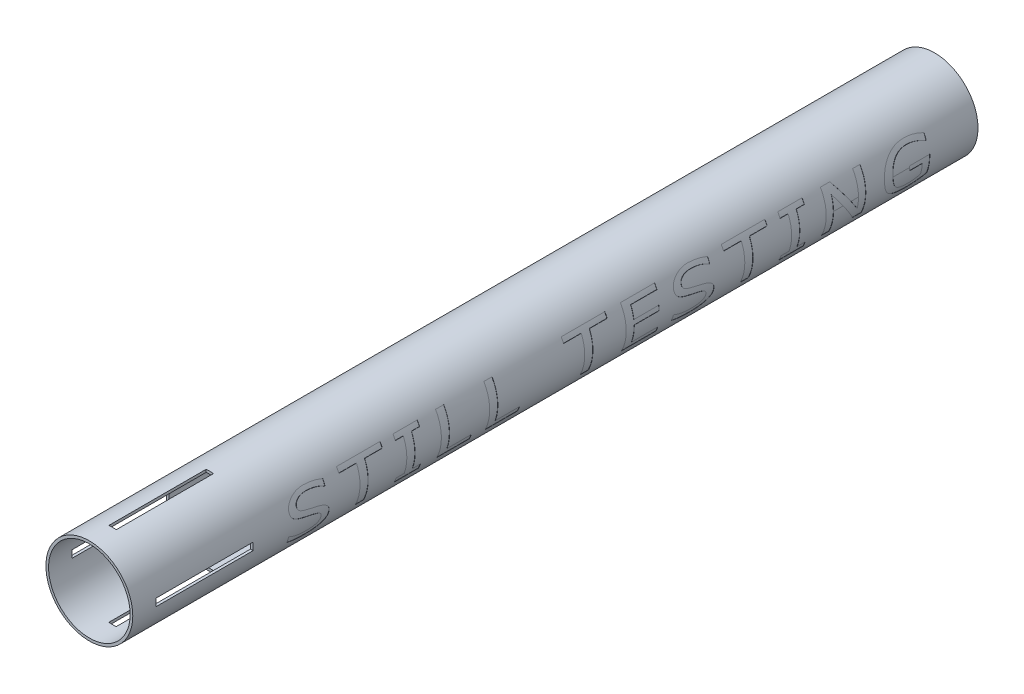
SolidWorks part; units mm, degrees
ref_plane "Front Plane" through (0, 0, 0) normal (0, 0, 1) x (1, 0, 0)
ref_plane "Top Plane" through (0, 0, 0) normal (0, 1, 0) x (1, 0, 0)
ref_plane "Right Plane" through (0, 0, 0) normal (1, 0, 0) x (0, 0, -1)
sketch "Sketch1" plane through (0, 0, 0) normal (0, 0, 1) x (1, 0, 0)
  circle A0 centre (0, 0) radius 20.555
  circle A1 centre (0, 0) radius 19.305
  dimension "D1" = 41.11
  dimension "D2" = 38.61
extrude "Boss-Extrude3" add sketch "Sketch1" against normal blind 400
sketch "Sketch2" plane through (0, 0, 0) normal (0, 1, 0) x (1, 0, 0)
  line L0 (0, -22.6105) -> (0, 22.6105) construction
  line L1 (-1.75, 57) -> (1.75, 57)
  line L2 (-1.75, 57) -> (-1.75, 11)
  line L3 (-1.75, 11) -> (1.75, 11)
  line L4 (1.75, 57) -> (1.75, 11)
  line L5 (-1.75, 57) -> (1.75, 11) construction
  line L6 (-1.75, 11) -> (1.75, 57) construction
  line L7 (-22.6105, 0) -> (22.6105, 0) construction
  point P0 (0, 34)
  dimension "D1" = 3.5
  dimension "D2" = 46
  dimension "D3" = 11
extrude "Cut-Extrude1" cut sketch "Sketch2" against normal through all both and the other way through all
pattern_circular "CirPattern1" count 2 over 90 about axis through (0, 0, -400) along (0, 0, 1) of "Cut-Extrude1" reverse direction yes
sketch "Sketch3" plane through (0, 0, 0) normal (1, 0, 0) x (0, 0, -1)
  text T0 "STILL TESTING" font "Verdana Pro Cond" height in points 72
extrude "Cut-Extrude2" cut sketch "Sketch3" along normal through all
sketch "Sketch4" plane through (0, 0, -400) normal (0, 0, -1) x (-1, 0, 0)
  circle A0 centre (0, 0) radius 19.305
  circle A1 centre (0, 0) radius 20.455
  circle A2 centre (0, 0) radius 19.305 construction
  circle A3 centre (0, 0) radius 20.555 construction
  dimension "D1" = 0.1
extrude "Boss-Extrude4" add sketch "Sketch4" against normal up to surface (343 mm away) up to face at (-19.8915, 0, -57)
